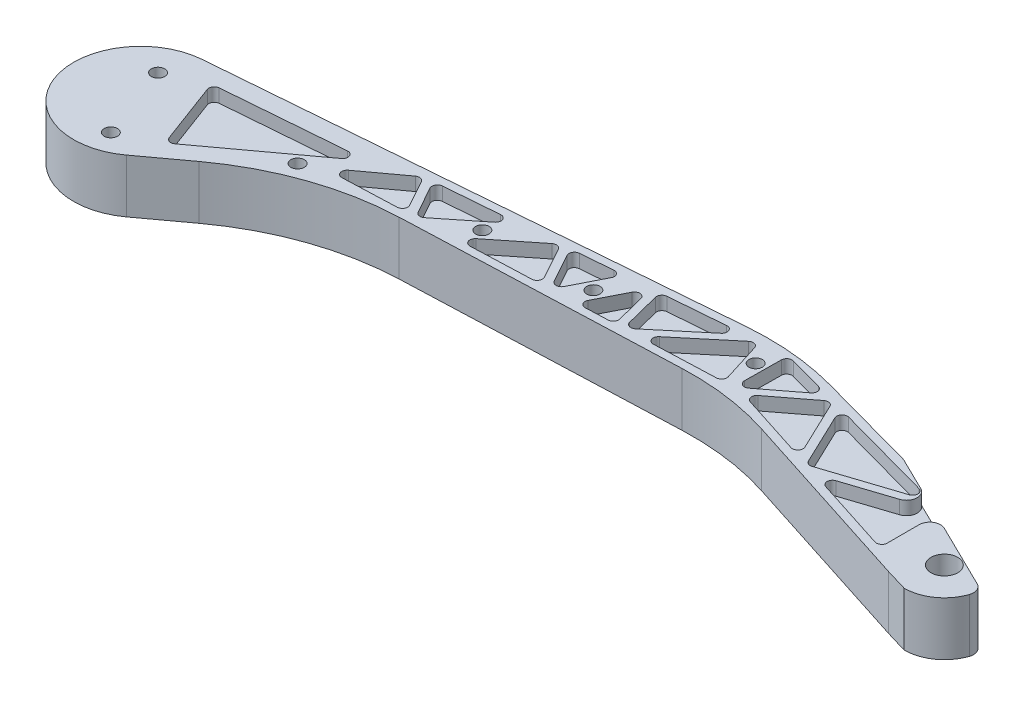
SolidWorks part; units mm, degrees
ref_plane "Front Plane" through (0, 0, 0) normal (0, 0, 1) x (1, 0, 0)
ref_plane "Top Plane" through (0, 0, 0) normal (0, 1, 0) x (1, 0, 0)
ref_plane "Right Plane" through (0, 0, 0) normal (1, 0, 0) x (0, 0, -1)
sketch "Sketch1" plane through (0, 0, 0) normal (0, 1, 0) x (1, 0, 0)
  line L0 (0, 0) -> (-300, 0) construction
  line L1 (0, 0) -> (35, 0) construction
  line L4 (-302.0128, 24.9188) -> (-285.1961, -20.1456) construction
  line L5 (-96.4179, 41.5254) -> (-717.946, -8.6774)
  line L6 (0, 15) -> (-657.0371, 195.7568)
  line L7 (0, 15) -> (-8.2094, -12.5541) construction
  line L8 (-717.946, -8.6774) -> (-94.8534, 15.2636)
  line L9 (-657.0371, 195.7568) -> (-8.2094, -12.5541)
  line L10 (-285.1961, -20.1456) -> (-244.8534, 9.5002)
  line L11 (-8.2094, -12.5541) -> (0, -15)
  circle A0 centre (0, 0) radius 5
  circle A1 centre (-300, 0) radius 25
  circle A3 centre (0, 0) radius 15
  dimension "D1" = 10
  dimension "D5" = 50
  dimension "D6" = 30
  dimension "D7" = 160
  dimension "D2" = 300
  dimension "D3" = 35
  dimension "D8" = 160
  dimension "D9" = 100
  dimension "D10" = 150
  dimension "D11" = 91
extrude "Boss-Extrude1" add sketch "Sketch1" along normal blind 10 and the other way blind 10 contours L8 A1 | A1 L8 | A1 L8 L9 L5 | A1 L10 L8 | A3 L6 L5 L9 | A3 A0 | A3 region at (-69.8594, 0, -19.9268) region at (-200.8967, 0, -21.2858) region at (10.3066, 0, -10.3066) region at (-300.5642, 0, -14.6835) region at (-299.7406, 0, 6.7503) region at (-265.9012, 0, -0.8715)
fillet "Fillet1" radius 100 4 edges at (-96.4179, 0, -41.5254) (-94.8534, 0, -15.2636) (-244.8534, 0, -9.5002) (0, 0, -15)
sketch "Sketch2" plane through (0, 10, 0) normal (0, 1, 0) x (1, 0, 0)
  line L0 (-285.1961, -20.1456) -> (-302.0128, 24.9188) construction
  line L1 (-292.2159, 18.6874) -> (-281.8765, -9.0194)
  line L2 (-281.8765, -9.0194) -> (-238.2394, 23.0472)
  line L3 (-238.2394, 23.0472) -> (-292.2159, 18.6874)
  line L4 (-285.1961, -20.1456) -> (-269.5743, -8.666) construction
  line L5 (-113.9933, 40.1058) -> (-302.0128, 24.9188) construction
  line L6 (-17.7547, 16.773) -> (-17.7547, -6.3387)
  line L7 (-17.7547, -6.3387) -> (-53.3654, 5.0944)
  line L8 (-53.3654, 5.0944) -> (-17.7547, 16.773)
  line L9 (-22.99, 18.2133) -> (-69.8958, 31.1175)
  line L10 (-69.8958, 31.1175) -> (-58.2301, 6.6562)
  line L11 (-58.2301, 6.6562) -> (-22.99, 18.2133)
  line L12 (-62.1547, 7.9163) -> (-73.7214, 32.17)
  line L13 (-73.7214, 32.17) -> (-92.6229, 17.6983)
  line L14 (-92.6229, 17.6983) -> (-62.1547, 7.9163)
  line L15 (-6.8698, 16.8899) -> (-79.4168, 36.8483) construction
  line L16 (-78.0647, 9.8735) -> (-8.2094, -12.5541) construction
  line L17 (-86.3511, 35.6445) -> (-12.0577, 15.2057) construction
  line L18 (-62.1547, 7.9163) -> (-53.3654, 5.0944) construction
  line L19 (-77.3519, 33.1687) -> (-96.9203, 18.1864)
  line L20 (-96.9203, 18.1864) -> (-244.1063, 12.5311) construction
  line L21 (-244.1063, 12.5311) -> (-222.6175, 28.3221)
  line L22 (-222.6175, 28.3221) -> (-96.7036, 38.4926) construction
  line L23 (-96.7036, 38.4926) -> (-77.3519, 33.1687)
  line L24 (-214.1981, 10.678) -> (-112.4731, 14.5866) construction
  line L25 (-96.7036, 38.4926) -> (-96.9203, 18.1864)
  line L26 (-106.5555, 37.6968) -> (-100.4103, 18.0523)
  line L27 (-100.4103, 18.0523) -> (-131.5203, 16.857)
  line L28 (-131.5203, 16.857) -> (-106.5555, 37.6968)
  line L29 (-111.7384, 37.2782) -> (-136.4276, 16.6684)
  line L30 (-136.4276, 16.6684) -> (-141.0342, 34.9118)
  line L31 (-141.0342, 34.9118) -> (-111.7384, 37.2782)
  line L32 (-144.0665, 34.6669) -> (-139.492, 16.5507)
  line L33 (-139.492, 16.5507) -> (-153.57, 16.0097)
  line L34 (-153.57, 16.0097) -> (-144.0665, 34.6669)
  line L35 (-153.4298, 33.9106) -> (-162.7272, 15.6579)
  line L36 (-162.7272, 15.6579) -> (-172.0207, 32.409)
  line L37 (-172.0207, 32.409) -> (-153.4298, 33.9106)
  line L38 (-175.3044, 32.1437) -> (-166.0864, 15.5288)
  line L39 (-166.0864, 15.5288) -> (-197.6515, 14.316)
  line L40 (-197.6515, 14.316) -> (-175.3044, 32.1437)
  line L41 (-222.6175, 28.3221) -> (-214.488, 13.6691)
  line L42 (-214.488, 13.6691) -> (-244.1063, 12.5311)
  line L43 (-219.3339, 28.5873) -> (-211.1288, 13.7982)
  line L44 (-211.1288, 13.7982) -> (-189.5777, 30.9908)
  line L45 (-189.5777, 30.9908) -> (-219.3339, 28.5873)
  line L46 (-194.4361, 21.9981) -> (-196.9306, 25.125) construction
  line L47 (-154.3314, 23.3279) -> (-150.7671, 21.5123) construction
  line L48 (-305.8804, 12.4012) -> (-295.3918, -15.7056) construction
  line L49 (-250.479, 9.0891) -> (-252.8476, 12.3124) construction
  circle A0 centre (-100.4103, 29.9667) radius 2.5
  circle A1 centre (-154.3314, 23.3279) radius 2.5
  circle A2 centre (-194.4361, 21.9981) radius 2.5
  circle A3 centre (-250.479, 9.0891) radius 2.5
  circle A4 centre (-305.8804, 12.4012) radius 2.5
  circle A5 centre (-295.3918, -15.7056) radius 2.5
  dimension "D14" = 5
  dimension "D25" = 4
  dimension "D1" = 7
  dimension "D2" = 7
  dimension "D3" = 7
  dimension "D4" = 3
  dimension "D5" = 3
  dimension "D6" = 3
  dimension "D7" = 3
  dimension "D8" = 32
  dimension "D9" = 3
  dimension "D10" = 3
  dimension "D11" = 3
  dimension "D12" = 3
  dimension "D13" = 5
  dimension "D15" = 3
  dimension "D16" = 3
  dimension "D17" = 3
  dimension "D18" = 3
  dimension "D19" = 8
  dimension "D20" = 8
  dimension "D21" = 4
  dimension "D22" = 4
  dimension "D23" = 8
  dimension "D24" = 30
extrude "Cut-Extrude1" cut sketch "Sketch2" against normal blind 5
fillet "Fillet2" radius 2 36 edges at (-17.7547, 7.5, 6.3387) (-17.7547, 7.5, -16.773) (-22.99, 7.5, -18.2133) (-58.2301, 7.5, -6.6562) (-69.8958, 7.5, -31.1175) (-62.1547, 7.5, -7.9163) (-92.6229, 7.5, -17.6983) (-73.7214, 7.5, -32.17) (-77.3519, 7.5, -33.1687) (-96.9203, 7.5, -18.1864) (-96.7036, 7.5, -38.4926) (-106.5555, 7.5, -37.6968) (-131.5203, 7.5, -16.857) (-100.4103, 7.5, -18.0523) (-141.0342, 7.5, -34.9118) (-136.4276, 7.5, -16.6684) (-111.7384, 7.5, -37.2782) (-153.57, 7.5, -16.0097) (-139.492, 7.5, -16.5507) (-144.0665, 7.5, -34.6669) (-172.0207, 7.5, -32.409) (-162.7272, 7.5, -15.6579) (-153.4298, 7.5, -33.9106) (-189.5777, 7.5, -30.9908) (-219.3339, 7.5, -28.5873) (-211.1288, 7.5, -13.7982) (-197.6515, 7.5, -14.316) (-175.3044, 7.5, -32.1437) (-166.0864, 7.5, -15.5288) (-214.488, 7.5, -13.6691) (-244.1063, 7.5, -12.5311) (-222.6175, 7.5, -28.3221) (-281.8765, 7.5, 9.0194) (-292.2159, 7.5, -18.6874) (-238.2394, 7.5, -23.0472) (-53.3654, 7.5, -5.0944)
mirror "Mirror2" about plane through (0, 0, 0) normal (0, 1, 0) of "Fillet2", "Cut-Extrude1"
sketch "Sketch3" plane through (0, 10, 0) normal (0, 1, 0) x (1, 0, 0)
  line L0 (-41.7074, 26.4741) -> (14.9447, -1.2866)
  line L1 (-6.8698, 16.8899) -> (-79.4168, 36.8483) construction
  line L2 (14.9447, -1.2866) -> (35.099, 39.8428)
  line L3 (35.099, 39.8428) -> (-41.7074, 26.4741)
  arc A0 (0, -15) -> (2.5638, 14.7793) centre (0, 0) ccw construction
extrude "Cut-Extrude2" cut sketch "Sketch3" against normal blind 20
fillet "Fillet5" radius 4 5 edges at (14.9447, 0, 1.2866) (-20.2372, -7.5, -15.9532) (-17.9252, -7.5, -14.8203) (-20.2372, 7.5, -15.9532) (-17.9252, 7.5, -14.8203)
